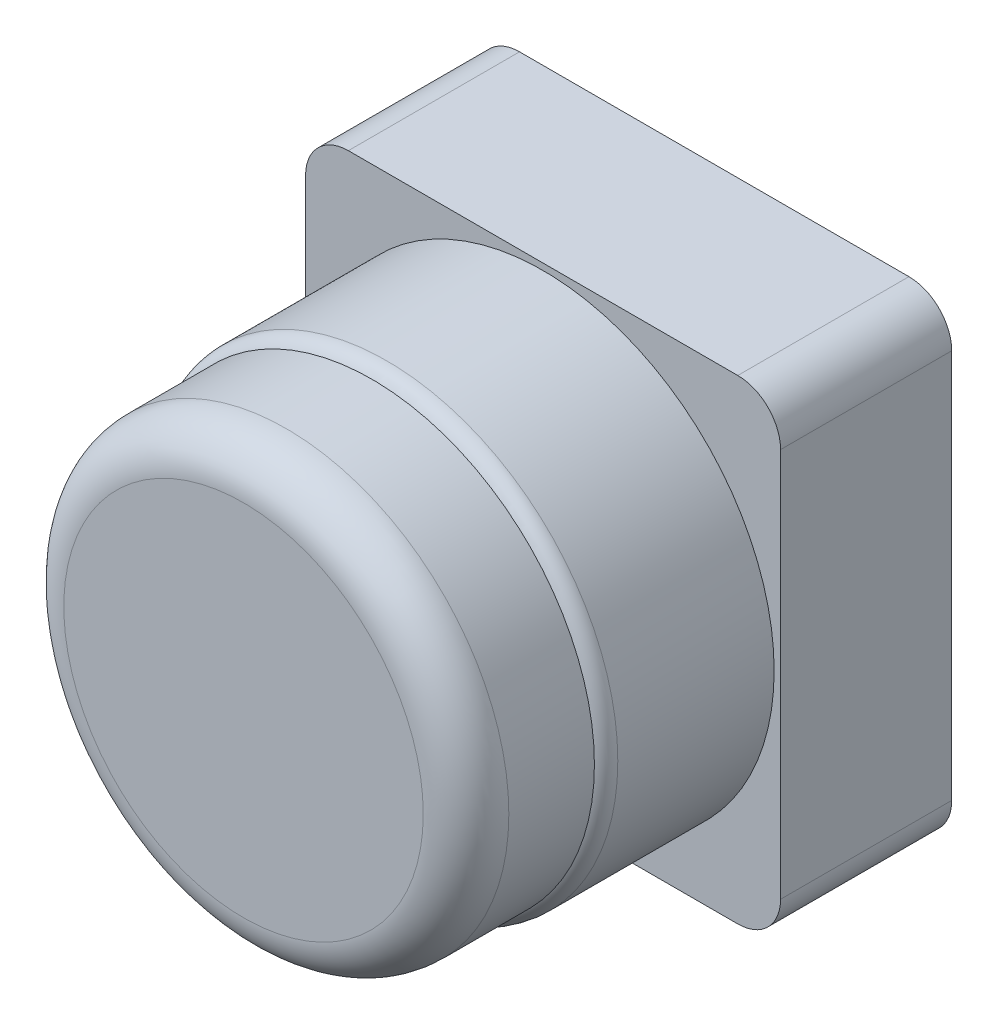
SolidWorks part; units mm, degrees
ref_plane "前视基准面" through (0, 0, 0) normal (0, 0, 1) x (1, 0, 0)
ref_plane "上视基准面" through (0, 0, 0) normal (0, 1, 0) x (1, 0, 0)
ref_plane "右视基准面" through (0, 0, 0) normal (1, 0, 0) x (0, 0, -1)
sketch "草图1" plane through (0, 0, 0) normal (0, 0, 1) x (1, 0, 0)
  line L0 (0, 0) -> (42151.9213, 0) construction
  line L1 (0, 0) -> (0, 42151.9213) construction
  line L3 (-27.75, 27.75) -> (27.75, 27.75)
  line L4 (-27.75, 27.75) -> (-27.75, -27.75)
  line L5 (-27.75, -27.75) -> (27.75, -27.75)
  line L6 (27.75, 27.75) -> (27.75, -27.75)
  dimension "D1" = 55.5
extrude "凸台-拉伸1" add sketch "草图1" along normal blind 20
sketch "草图2" plane through (0, 0, 20) normal (0, 0, 1) x (1, 0, 0)
  circle A0 centre (0, 0) radius 27
extrude "凸台-拉伸3" add sketch "草图2" along normal blind 20
sketch "草图3" plane through (0, 0, 40) normal (0, 0, 1) x (1, 0, 0)
  circle A0 centre (0, 0) radius 26
extrude "凸台-拉伸6" add sketch "草图3" along normal blind 15
fillet "圆角1" radius 5 1 edges at (26, 0, 55)
fillet "圆角2" radius 2 1 edges at (27, 0, 40)
fillet "圆角3" radius 5 4 edges at (-27.75, 27.75, 10) (27.75, 27.75, 10) (27.75, -27.75, 10) (-27.75, -27.75, 10)
sketch "草图5" plane through (0, 0, 0) normal (0, 0, -1) x (-1, 0, 0)
  line L0 (0, 0) -> (0, 50000) construction
  line L1 (0, 0) -> (50000, 0) construction
  line L2 (0, 0) -> (35355.3391, 35355.3391) construction
  line L3 (1.3651, -1.3651) -> (-35353.974, 35353.974) construction
  line L4 (-22.75, 27.75) -> (22.75, 27.75) construction
  line L5 (-27.75, -22.75) -> (-27.75, 22.75) construction
  circle A0 centre (0, 0) radius 1.5
  circle A1 centre (-21.75, 21.75) radius 1.5
  circle A2 centre (21.75, 21.75) radius 1.5
  circle A3 centre (21.75, -21.75) radius 1.5
  circle A4 centre (-21.75, -21.75) radius 1.5
  dimension "D1" = 6
  dimension "D2" = 6
extrude "切除-拉伸1" cut sketch "草图5" against normal blind 10
sketch "草图6" plane through (0, -27.75, 0) normal (0, -1, 0) x (1, 0, 0)
  line L0 (0, -25.8763) -> (0, 25.8763) construction
  line L1 (-22.75, 0) -> (22.75, 0) construction
  line L2 (-5, 5) -> (5, 5)
  line L3 (-5, 5) -> (-5, 0)
  line L4 (-5, 0) -> (5, 0)
  line L5 (5, 5) -> (5, 0)
  line L7 (-5, 5) -> (5, 5)
  line L8 (-5, 5) -> (-5, 1)
  line L9 (-5, 1) -> (5, 1)
  line L10 (5, 5) -> (5, 1)
  point P4 (0, 0)
  dimension "D1" = 1
extrude "切除-拉伸2" cut sketch "草图6" against normal blind 4 contours L9 L0 L2 L3 | L0 L9 L5 L7 region at (-2.5, -27.75, 3) region at (2.5, -27.75, 3)
